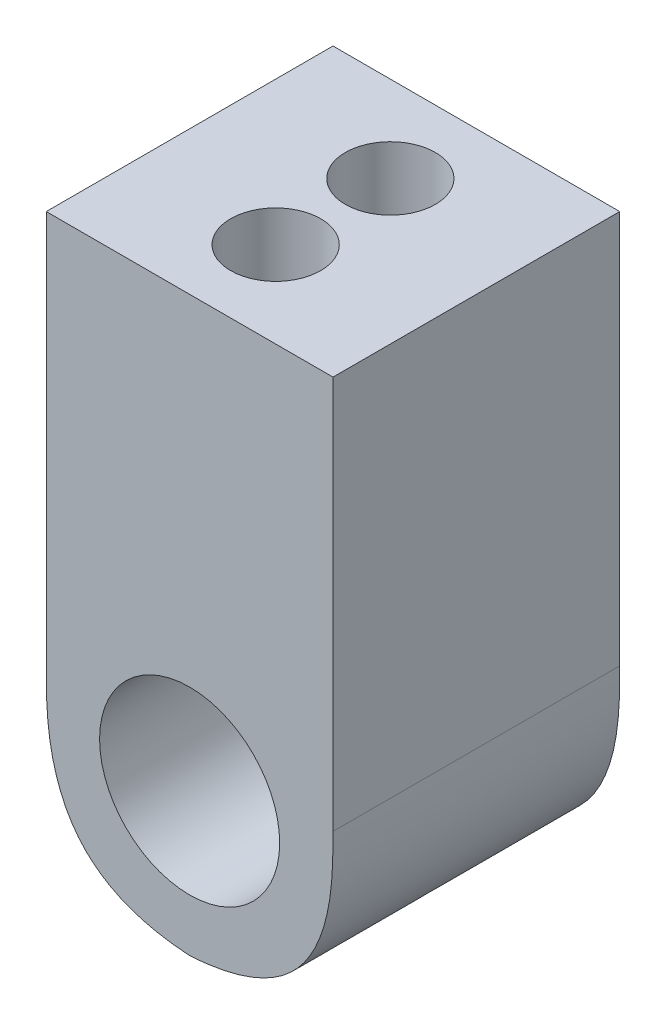
SolidWorks part; units mm, degrees
ref_plane "Front Plane" through (0, 0, 0) normal (0, 0, 1) x (1, 0, 0)
ref_plane "Top Plane" through (0, 0, 0) normal (0, 1, 0) x (1, 0, 0)
ref_plane "Right Plane" through (0, 0, 0) normal (1, 0, 0) x (0, 0, -1)
sketch "Sketch1" plane through (0, 0, 0) normal (0, 0, 1) x (1, 0, 0)
  line L1 (-6.35, 6.35) -> (6.35, 6.35)
  line L2 (-6.35, 6.35) -> (-6.35, -6.35)
  line L3 (-6.35, -6.35) -> (6.35, -6.35)
  line L4 (6.35, 6.35) -> (6.35, -6.35)
  line L5 (-6.35, 6.35) -> (6.35, -6.35) construction
  line L6 (-6.35, -6.35) -> (6.35, 6.35) construction
  line L7 (-6.35, 6.35) -> (6.35, 6.35)
  line L8 (-6.35, 6.35) -> (-6.35, 19.05)
  line L9 (-6.35, 19.05) -> (6.35, 19.05)
  line L10 (6.35, 6.35) -> (6.35, 19.05)
  circle A0 centre (0, 0) radius 3.9878
  point P0 (0, 0)
  dimension "D2" = 7.9756
  dimension "D1" = 12.7
  dimension "D3" = 12.7
  dimension "D4" = 12.7
extrude "Boss-Extrude1" add sketch "Sketch1" against normal blind 12.7 contours L1 L10 L9 L8 | L4 L1 L2 L3 A0 | A0 region at (0, 12.7, 0) region at (0, 6.1704, 0) region at (0, 0, 0)
fillet "Fillet1" radius 7.9756 2 edges at (-6.35, -6.35, -6.35) (6.35, -6.35, -6.35) curvature continuous yes
sketch "Sketch3" plane through (0, 19.05, 0) normal (0, 1, 0) x (1, 0, 0)
  line L0 (0, 12.7) -> (0, 0) construction
  line L1 (6.35, 8.89) -> (-6.35, 8.89)
  line L2 (-6.35, 3.81) -> (6.35, 3.81)
  line L4 (-6.35, 0) -> (6.35, 0)
  line L5 (6.35, 0) -> (6.35, 12.7)
  line L6 (6.35, 12.7) -> (-6.35, 12.7)
  line L7 (-6.35, 12.7) -> (-6.35, 0)
  line L8 (-6.35, 0) -> (6.35, 0)
  line L9 (6.35, 0) -> (6.35, 12.7)
  line L10 (6.35, 12.7) -> (-6.35, 12.7)
  line L11 (-6.35, 12.7) -> (-6.35, 0)
  circle A0 centre (0, 8.89) radius 1.9939
  circle A1 centre (0, 3.81) radius 1.9939
  dimension "D3" = 3.9878
  dimension "D4" = 3.9878
  dimension "D2" = 3.81
  dimension "D1" = 0
extrude "Cut-Extrude2" cut sketch "Sketch3" against normal blind 6.35 contours L1 L0 A0 | A0 L0 L1 | L0 A0 L1 | L0 L1 A0 | A1 L0 L2 | L2 L0 A1 | L0 L2 A1 | L0 A1 L2 region at (0.8462, 19.05, -9.7362) region at (-0.8462, 19.05, -9.7362) region at (0.8462, 19.05, -8.0438) region at (-0.8462, 19.05, -8.0438) region at (0.8462, 19.05, -4.6562) region at (-0.8462, 19.05, -4.6562) region at (0.8462, 19.05, -2.9638) region at (-0.8462, 19.05, -2.9638)
extrude "Cut-Extrude3" cut sketch "Sketch1<3>" against normal through all contours A0
sketch "Sketch1<3>" plane through (0, 0, 0) normal (0, 0, 1) x (1, 0, 0) same geometry as "Sketch1"
